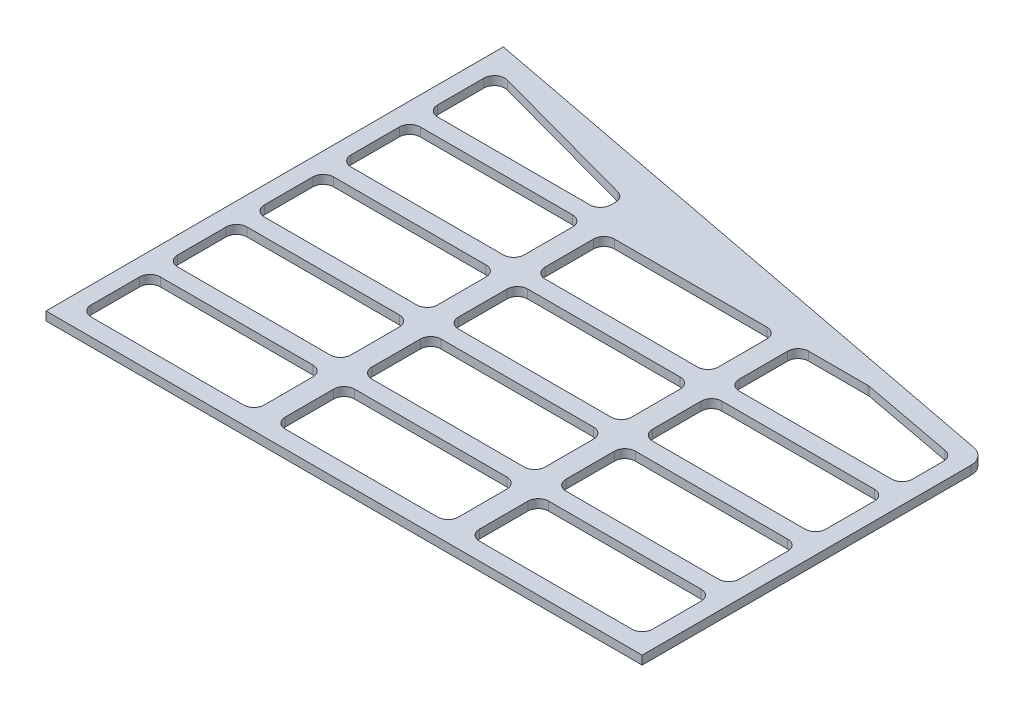
SolidWorks part; units mm, degrees
material "Balsa"
ref_plane "Front Plane" through (0, 0, 0) normal (0, 0, 1) x (1, 0, 0)
ref_plane "Top Plane" through (0, 0, 0) normal (0, 1, 0) x (1, 0, 0)
ref_plane "Right Plane" through (0, 0, 0) normal (1, 0, 0) x (0, 0, -1)
sketch "Sketch1" plane through (0, 0, 0) normal (0, 1, 0) x (1, 0, 0)
  line L0 (0, 0) -> (437.0222, 0)
  line L1 (426.7145, 253.437) -> (0, 335.28)
  line L2 (0, 335.28) -> (0, 0)
  line L3 (437.0222, 0) -> (437.0222, 240.9644)
  arc A0 (426.7145, 253.437) -> (437.0222, 240.9644) centre (424.3222, 240.9644) cw
  point P7 (437.0222, 251.46)
  dimension "D4" = 12.7
  dimension "D1" = 335.28
  dimension "D2" = 437.0222
  dimension "D3" = 251.46
extrude "Boss-Extrude1" add sketch "Sketch1" along normal blind 6.35
sketch "Sketch2" plane through (0, 6.35, 0) normal (0, 1, 0) x (1, 0, 0)
  line L0 (0, 0) -> (437.0222, 0) construction
  line L1 (20.32, 12.7) -> (132.08, 12.7)
  line L2 (12.7, 20.32) -> (12.7, 55.88)
  line L3 (20.32, 63.5) -> (132.08, 63.5)
  line L4 (139.7, 20.32) -> (139.7, 55.88)
  line L9 (0, 335.28) -> (0, 0) construction
  line L10 (155.045, 20.32) -> (155.045, 55.88)
  line L11 (162.665, 12.7) -> (274.425, 12.7)
  line L12 (282.045, 20.32) -> (282.045, 55.88)
  line L13 (162.665, 63.5) -> (274.425, 63.5)
  line L14 (297.3901, 20.32) -> (297.3901, 55.88)
  line L15 (305.0101, 12.7) -> (416.7701, 12.7)
  line L16 (424.3901, 20.32) -> (424.3901, 55.88)
  line L17 (305.0101, 63.5) -> (416.7701, 63.5)
  line L18 (155.045, 83.82) -> (155.045, 119.38)
  line L19 (162.665, 76.2) -> (274.425, 76.2)
  line L20 (282.045, 83.82) -> (282.045, 119.38)
  line L21 (162.665, 127) -> (274.425, 127)
  line L22 (297.3901, 83.82) -> (297.3901, 119.38)
  line L23 (305.0101, 76.2) -> (416.7701, 76.2)
  line L24 (424.3901, 83.82) -> (424.3901, 119.38)
  line L25 (305.0101, 127) -> (416.7701, 127)
  line L26 (155.045, 147.32) -> (155.045, 182.88)
  line L27 (162.665, 139.7) -> (274.425, 139.7)
  line L28 (282.045, 147.32) -> (282.045, 182.88)
  line L29 (162.665, 190.5) -> (274.425, 190.5)
  line L30 (297.3901, 147.32) -> (297.3901, 182.88)
  line L31 (305.0101, 139.7) -> (416.7701, 139.7)
  line L32 (424.3901, 147.32) -> (424.3901, 182.88)
  line L33 (305.0101, 190.5) -> (416.7701, 190.5)
  line L34 (155.045, 210.82) -> (155.045, 246.38)
  line L35 (162.665, 203.2) -> (274.425, 203.2)
  line L36 (282.045, 210.82) -> (282.045, 246.38)
  line L37 (162.665, 254) -> (274.425, 254)
  line L38 (297.3901, 210.82) -> (297.3901, 246.38)
  line L39 (305.0101, 203.2) -> (416.7701, 203.2)
  line L40 (424.3901, 210.82) -> (424.3901, 233.5456)
  line L41 (305.0101, 254) -> (348.5374, 254)
  line L50 (12.7, 83.82) -> (12.7, 119.38)
  line L51 (20.32, 76.2) -> (132.08, 76.2)
  line L52 (139.7, 83.82) -> (139.7, 119.38)
  line L53 (20.32, 127) -> (132.08, 127)
  line L54 (12.7, 147.32) -> (12.7, 182.88)
  line L55 (20.32, 139.7) -> (132.08, 139.7)
  line L56 (139.7, 147.32) -> (139.7, 182.88)
  line L57 (20.32, 190.5) -> (132.08, 190.5)
  line L58 (12.7, 210.8976) -> (12.7, 246.3024)
  line L59 (20.3976, 203.2) -> (132.0024, 203.2)
  line L60 (139.7, 210.8976) -> (139.7, 246.3024)
  line L61 (20.3976, 254) -> (132.0024, 254)
  line L62 (12.7, 274.3976) -> (12.7, 308.3078)
  line L63 (20.3976, 266.7) -> (132.0024, 266.7)
  line L64 (139.7, 274.3976) -> (139.7, 277.7658)
  line L66 (22.4294, 315.7324) -> (134.0343, 285.1904)
  line L68 (12.7, 317.5) -> (106.9847, 317.5) [skipped]
  line L69 (154.94, 317.5) -> (281.94, 317.5) [skipped]
  line L70 (282.045, 364.4738) -> (282.045, 415.2738) [skipped]
  line L71 (297.3901, 266.7) -> (297.3901, 317.5) [skipped]
  line L72 (297.18, 317.5) -> (424.18, 317.5) [skipped]
  line L73 (424.3901, 266.7) -> (424.3901, 317.5) [skipped]
  line L74 (297.18, 266.7) -> (424.18, 266.7) [skipped]
  line L75 (349.946, 253.8687) -> (418.1787, 241.0342)
  line L77 (162.665, 266.7) -> (200.4554, 266.7) [skipped]
  line L78 (155.045, 286.9363) -> (155.045, 297.2637) [skipped]
  arc A0 (20.32, 12.7) -> (12.7, 20.32) centre (20.32, 20.32) cw
  arc A1 (12.7, 55.88) -> (20.32, 63.5) centre (20.32, 55.88) cw
  arc A2 (132.08, 63.5) -> (139.7, 55.88) centre (132.08, 55.88) cw
  arc A3 (132.08, 12.7) -> (139.7, 20.32) centre (132.08, 20.32) ccw
  arc A4 (155.045, 20.32) -> (162.665, 12.7) centre (162.665, 20.32) ccw
  arc A5 (155.045, 55.88) -> (162.665, 63.5) centre (162.665, 55.88) cw
  arc A6 (282.045, 55.88) -> (274.425, 63.5) centre (274.425, 55.88) ccw
  arc A7 (274.425, 12.7) -> (282.045, 20.32) centre (274.425, 20.32) ccw
  arc A8 (416.7701, 12.7) -> (424.3901, 20.32) centre (416.7701, 20.32) ccw
  arc A9 (297.3901, 20.32) -> (305.0101, 12.7) centre (305.0101, 20.32) ccw
  arc A10 (297.3901, 55.88) -> (305.0101, 63.5) centre (305.0101, 55.88) cw
  arc A11 (424.3901, 55.88) -> (416.7701, 63.5) centre (416.7701, 55.88) ccw
  arc A12 (424.3901, 119.38) -> (416.7701, 127) centre (416.7701, 119.38) ccw
  arc A13 (416.7701, 76.2) -> (424.3901, 83.82) centre (416.7701, 83.82) ccw
  arc A14 (297.3901, 83.82) -> (305.0101, 76.2) centre (305.0101, 83.82) ccw
  arc A15 (297.3901, 119.38) -> (305.0101, 127) centre (305.0101, 119.38) cw
  arc A16 (282.045, 119.38) -> (274.425, 127) centre (274.425, 119.38) ccw
  arc A17 (282.045, 83.82) -> (274.425, 76.2) centre (274.425, 83.82) cw
  arc A18 (155.045, 83.82) -> (162.665, 76.2) centre (162.665, 83.82) ccw
  arc A19 (155.045, 119.38) -> (162.665, 127) centre (162.665, 119.38) cw
  arc A20 (139.7, 119.38) -> (132.08, 127) centre (132.08, 119.38) ccw
  arc A21 (132.08, 76.2) -> (139.7, 83.82) centre (132.08, 83.82) ccw
  arc A22 (12.7, 83.82) -> (20.32, 76.2) centre (20.32, 83.82) ccw
  arc A23 (12.7, 119.38) -> (20.32, 127) centre (20.32, 119.38) cw
  arc A24 (12.7, 147.32) -> (20.32, 139.7) centre (20.32, 147.32) ccw
  arc A25 (12.7, 182.88) -> (20.32, 190.5) centre (20.32, 182.88) cw
  arc A26 (139.7, 182.88) -> (132.08, 190.5) centre (132.08, 182.88) ccw
  arc A27 (132.08, 139.7) -> (139.7, 147.32) centre (132.08, 147.32) ccw
  arc A28 (155.045, 147.32) -> (162.665, 139.7) centre (162.665, 147.32) ccw
  arc A29 (155.045, 182.88) -> (162.665, 190.5) centre (162.665, 182.88) cw
  arc A30 (274.425, 139.7) -> (282.045, 147.32) centre (274.425, 147.32) ccw
  arc A31 (282.045, 182.88) -> (274.425, 190.5) centre (274.425, 182.88) ccw
  arc A32 (297.3901, 182.88) -> (305.0101, 190.5) centre (305.0101, 182.88) cw
  arc A33 (297.3901, 147.32) -> (305.0101, 139.7) centre (305.0101, 147.32) ccw
  arc A34 (416.7701, 139.7) -> (424.3901, 147.32) centre (416.7701, 147.32) ccw
  arc A35 (424.3901, 182.88) -> (416.7701, 190.5) centre (416.7701, 182.88) ccw
  arc A36 (418.1787, 241.0342) -> (424.3901, 233.5456) centre (416.7701, 233.5456) cw
  arc A37 (348.5374, 254) -> (349.946, 253.8687) centre (348.5374, 246.38) cw
  arc A38 (297.3901, 210.82) -> (305.0101, 203.2) centre (305.0101, 210.82) ccw
  arc A39 (416.7701, 203.2) -> (424.3901, 210.82) centre (416.7701, 210.82) ccw
  arc A40 (297.3901, 246.38) -> (305.0101, 254) centre (305.0101, 246.38) cw
  arc A41 (155.045, 246.38) -> (162.665, 254) centre (162.665, 246.38) cw
  arc A42 (155.045, 210.82) -> (162.665, 203.2) centre (162.665, 210.82) ccw
  arc A44 (274.425, 203.2) -> (282.045, 210.82) centre (274.425, 210.82) ccw
  arc A45 (282.045, 246.38) -> (274.425, 254) centre (274.425, 246.38) ccw
  arc A48 (139.7, 246.3024) -> (132.0024, 254) centre (132.0024, 246.3024) ccw
  arc A49 (132.0024, 203.2) -> (139.7, 210.8976) centre (132.0024, 210.8976) ccw
  arc A50 (12.7, 210.8976) -> (20.3976, 203.2) centre (20.3976, 210.8976) ccw
  arc A51 (12.7, 246.3024) -> (20.3976, 254) centre (20.3976, 246.3024) cw
  arc A52 (12.7, 274.3976) -> (20.3976, 266.7) centre (20.3976, 274.3976) ccw
  arc A53 (132.0024, 266.7) -> (139.7, 274.3976) centre (132.0024, 274.3976) ccw
  arc A54 (139.7, 277.7658) -> (134.0343, 285.1904) centre (132.0024, 277.7658) ccw
  arc A55 (12.7, 308.3078) -> (22.4294, 315.7324) centre (20.3976, 308.3078) cw
  point P46 (12.7, 12.7)
  point P49 (12.7, 63.5)
  point P82 (139.7, 63.5)
  dimension "D7" = 7.62
  dimension "D1" = 127
  dimension "D2" = 50.8
  dimension "D3" = 12.7
  dimension "D4" = 12.7
  dimension "D5" = 3
  dimension "D6" = 5
extrude "Cut-Extrude1" cut sketch "Sketch2" against normal up to surface (6.35 mm away) up to face at (260.6005, 0, -166.3071)
